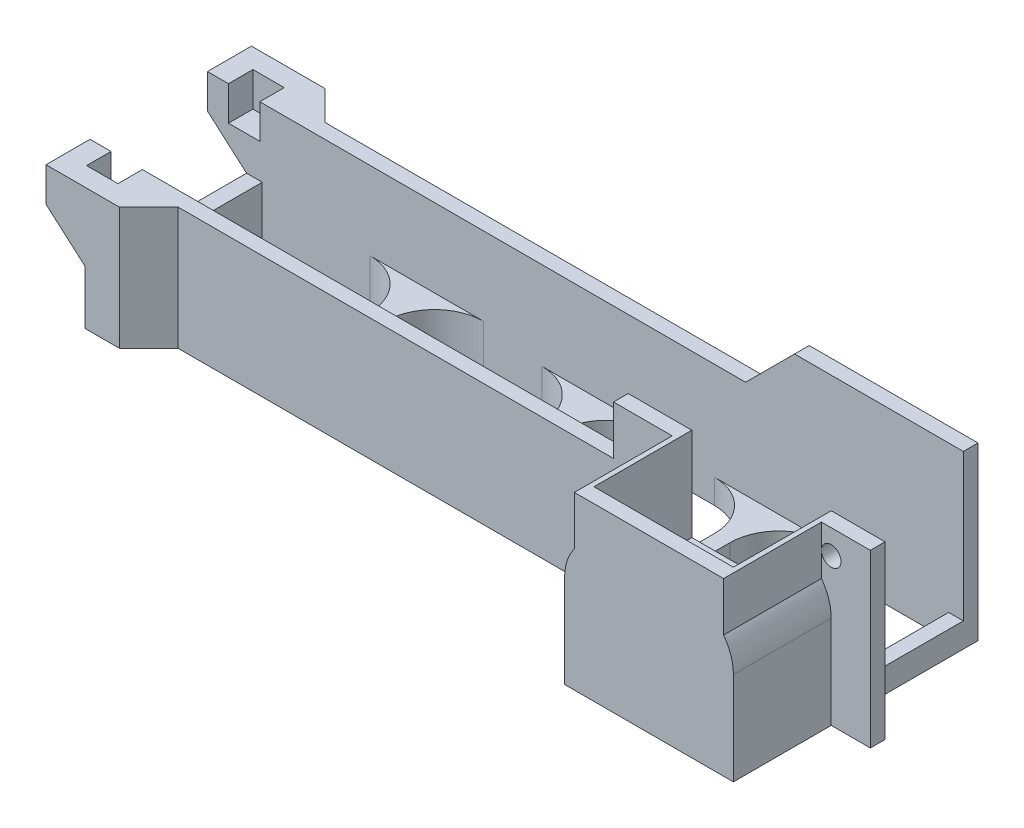
SolidWorks part; units mm, degrees
ref_plane "前视基准面" through (0, 0, 0) normal (0, 0, 1) x (1, 0, 0)
ref_plane "上视基准面" through (0, 0, 0) normal (0, 1, 0) x (1, 0, 0)
ref_plane "右视基准面" through (0, 0, 0) normal (1, 0, 0) x (0, 0, -1)
sketch "Sketch1" plane through (0, 0, 0) normal (0, 1, 0) x (1, 0, 0)
  line L1 (0, 0) -> (154.5, 0)
  line L2 (0, 0) -> (0, 30)
  line L3 (0, 30) -> (154.5, 30)
  line L4 (154.5, 0) -> (154.5, 30)
  line L5 (154.5, 0) -> (120, 0)
  line L6 (154.5, 0) -> (154.5, -20)
  line L7 (154.5, -20) -> (120, -20)
  line L8 (120, 0) -> (120, -20)
  dimension "D1" = 34.5
  dimension "D2" = 30
  dimension "D3" = 154.5
  dimension "D4" = 20
extrude "Boss-Extrude2" add sketch "Sketch1" along normal blind 1 contours L1 L4 L3 L2 | L1 L8 L7 L6 region at (77.25, 0, -15) region at (137.25, 0, 10)
sketch "Sketch2" plane through (0, 1, 0) normal (0, 1, 0) x (1, 0, 0)
  line L0 (3, 27) -> (0, 27)
  line L1 (0, 0) -> (120, 0)
  line L2 (120, 0) -> (120, -20) construction
  line L3 (0, 0) -> (120, 0) construction
  line L4 (120, 0) -> (120, -20)
  line L5 (120, -20) -> (154.5, -20)
  line L6 (0, 27) -> (0, 30)
  line L7 (154.5, 30) -> (0, 30)
  line L8 (151.5, 27) -> (154.5, 27)
  line L9 (3, 3) -> (123, 3)
  line L10 (123, 3) -> (123, -17)
  line L11 (123, -17) -> (151.5, -17)
  line L12 (154.5, -20) -> (154.5, 30) construction
  line L13 (151.5, 27) -> (3, 27)
  line L14 (3, 27) -> (3, 3) construction
  line L15 (0, 30) -> (0, 0) construction
  line L16 (151.5, -17) -> (151.5, 27) construction
  line L17 (154.5, -20) -> (154.5, 30) construction
  line L18 (154.5, 27) -> (154.5, 30)
  line L19 (151.5, -17) -> (151.5, 3)
  line L20 (151.5, 3) -> (154.5, 3)
  line L21 (154.5, 3) -> (154.5, -20)
  line L22 (3, 3) -> (0, 3)
  line L23 (0, 0) -> (0, 30) construction
  line L24 (0, 3) -> (0, 0)
  dimension "D1" = 3
extrude "Boss-Extrude5" add sketch "Sketch2" along normal blind 24
sketch "Sketch5" plane through (0, 0, -27) normal (0, 0, 1) x (1, 0, 0)
  line L0 (0, 0) -> (120, 0) construction
  line L1 (8, 1) -> (11.2, 1)
  line L2 (8, 1) -> (8, 11)
  line L3 (8, 11) -> (11.2, 11)
  line L4 (11.2, 1) -> (11.2, 11)
  line L8 (43.2, 1) -> (46.4, 1)
  line L9 (43.2, 1) -> (43.2, 9)
  line L10 (43.2, 9) -> (46.4, 9)
  line L11 (46.4, 1) -> (46.4, 9)
  line L12 (78.4, 1) -> (81.6, 1)
  line L13 (78.4, 1) -> (78.4, 7)
  line L14 (78.4, 7) -> (81.6, 7)
  line L15 (81.6, 1) -> (81.6, 7)
  line L16 (113.6, 1) -> (116.8, 1)
  line L17 (113.6, 1) -> (113.6, 5)
  line L18 (113.6, 5) -> (116.8, 5)
  line L19 (116.8, 1) -> (116.8, 5)
  line L20 (0, 25) -> (0, 0) construction
  line L21 (154.5, 1) -> (151.5, 1)
  line L22 (154.5, 1) -> (154.5, 5)
  line L23 (154.5, 5) -> (151.5, 5)
  line L26 (151.5, 1) -> (151.5, 5)
  dimension "D1" = 8
  dimension "D2" = 10
  dimension "D3" = 3.2
  dimension "D4" = 8
  dimension "D5" = 6
  dimension "D6" = 4
  dimension "D7" = 1
  dimension "D8" = 32
  dimension "D9" = 32
  dimension "D10" = 32
extrude "Boss-Extrude6" add sketch "Sketch5" along normal blind 24
sketch "Sketch6" plane through (0, 1, 0) normal (0, 1, 0) x (1, 0, 0)
  line L1 (123, 3) -> (151.5, 3)
  line L2 (123, 3) -> (123, -17)
  line L3 (123, -17) -> (151.5, -17)
  line L4 (151.5, 3) -> (151.5, -17)
extrude "Boss-Extrude7" add sketch "Sketch6" along normal blind 15
sketch "Sketch7" plane through (0, 25, 0) normal (0, 1, 0) x (1, 0, 0)
  line L0 (110, 3) -> (110, 0)
  line L1 (110, 0) -> (122, 0)
  line L2 (122, 0) -> (122, -20)
  line L3 (122, -20) -> (152.5, -20)
  line L4 (152.5, -20) -> (152.5, 0)
  line L6 (152.5, 0) -> (162.5, 0)
  line L7 (162.5, 0) -> (162.5, 3)
  line L8 (162.5, 3) -> (151.5, 3)
  line L9 (151.5, 3) -> (151.5, -17)
  line L10 (151.5, -17) -> (123, -17)
  line L11 (123, -17) -> (123, 3)
  line L12 (123, 3) -> (110, 3)
  dimension "D1" = 1
extrude "Boss-Extrude8" add sketch "Sketch7" along normal blind 10
sketch "Sketch9" plane through (0, 25, 0) normal (0, -1, 0) x (1, 0, 0)
  line L1 (154.5, -3) -> (162.5, -3)
  line L2 (154.5, -3) -> (154.5, 0)
  line L3 (154.5, 0) -> (162.5, 0)
  line L4 (162.5, -3) -> (162.5, 0)
extrude "Boss-Extrude9" add sketch "Sketch9" along normal blind 25
sketch "Sketch10" plane through (0, 0, -3) normal (0, 0, -1) x (-1, 0, 0)
  line L0 (-123, 16) -> (-123, 30) construction
  line L1 (-123, 35) -> (-123, 16) construction
  line L2 (-123, 30) -> (-120, 30) construction
  line L3 (-151.5, 16) -> (-151.5, 30) construction
  line L4 (-151.5, 35) -> (-151.5, 16) construction
  line L5 (-151.5, 30) -> (-154.5, 30) construction
  circle A0 centre (-120, 30) radius 2
  circle A1 centre (-154.5, 30) radius 2
extrude "Cut-Extrude1" cut sketch "Sketch10" against normal blind 8
sketch "Sketch11" plane through (0, 1, 0) normal (0, 1, 0) x (1, 0, 0)
  line L0 (11.2, 27) -> (43.2, 27)
  line L1 (43.2, 3) -> (11.2, 3)
  line L2 (11.2, 27) -> (11.2, 3)
  line L8 (43.2, 27) -> (43.2, 3)
  line L9 (46.4, 27) -> (78.4, 27)
  line L10 (46.4, 27) -> (46.4, 3)
  line L11 (46.4, 3) -> (78.4, 3)
  line L12 (78.4, 27) -> (78.4, 3)
  line L13 (81.6, 27) -> (113.6, 27)
  line L14 (81.6, 27) -> (81.6, 3)
  line L15 (81.6, 3) -> (113.6, 3)
  line L16 (113.6, 27) -> (113.6, 3)
  line L17 (116.8, 27) -> (151.5, 27)
  line L18 (116.8, 27) -> (116.8, 3)
  line L19 (116.8, 3) -> (151.5, 3)
  line L20 (151.5, 27) -> (151.5, 3)
extrude "Cut-Extrude2" cut sketch "Sketch11" against normal blind 8
fillet "Fillet1" radius 10 14 edges at (154.5, 25, 10) (120, 25, 10) (46.4, 4.5, -3) (81.6, 3.5, -3) (116.8, 2.5, -3) (113.6, 2.5, -27) (78.4, 3.5, -27) (43.2, 4.5, -27) (43.2, 4.5, -3) (113.6, 2.5, -3) (78.4, 3.5, -3) (46.4, 4.5, -27) (81.6, 3.5, -27) (116.8, 2.5, -27)
sketch "Sketch13" plane through (0, 0, 0) normal (0, -1, 0) x (1, 0, 0)
  line L2 (0, 0) -> (15, 0)
  line L3 (0, 0) -> (0, 6)
  line L4 (0, 6) -> (15, 6)
  line L5 (15, 0) -> (15, 6)
  dimension "D1" = 15
  dimension "D2" = 6
extrude "Boss-Extrude10" add sketch "Sketch13" against normal up to surface (25 mm away) up to face at (55, 25, -1.5)
sketch "Sketch15" plane through (0, 25, 0) normal (0, 1, 0) x (1, 0, 0)
  line L0 (110, 3) -> (0, 3) construction
  line L1 (4.3, 3) -> (10.7, 3)
  line L2 (4.3, 3) -> (4.3, -2)
  line L3 (4.3, -2) -> (10.7, -2)
  line L4 (10.7, 3) -> (10.7, -2)
  line L6 (15, -6) -> (0, -6) construction
  line L7 (7.5, -6) -> (7.5, 3) construction
  dimension "D1" = 6.4
  dimension "D2" = 5
extrude "Cut-Extrude3" cut sketch "Sketch15" against normal blind 7
ref_plane "Plane1" through (0, 0, -15) normal (0, 0, 1) x (1, 0, 0)
mirror "Mirror1" about plane through (0, 0, -15) normal (0, 0, 1) of "Cut-Extrude3", "Boss-Extrude10"
sketch "Sketch16" plane through (0, 0, -3) normal (0, 0, -1) x (-1, 0, 0)
  line L0 (-8, 11) -> (0, 18)
  line L1 (0, 25) -> (0, 1) construction
  line L2 (0, 18) -> (0, 0)
  line L3 (-8, 11) -> (-8, 0)
  line L4 (-15, 0) -> (-154.5, 0) construction
  line L5 (-8, 0) -> (0, 0)
  dimension "D1" = 18
extrude "Cut-Extrude4" cut sketch "Sketch16" against normal through all and the other way through all
chamfer "Chamfer1" distance 6 2 edges at (15, 12.5, 0)
sketch "Sketch17" plane through (0, 25, 0) normal (0, 1, 0) x (1, 0, 0)
  line L0 (10.7, 27) -> (154.5, 27) construction
  line L1 (154.5, 30) -> (120, 30)
  line L2 (154.5, 30) -> (154.5, 27)
  line L3 (154.5, 27) -> (120, 27)
  line L4 (120, 30) -> (120, 27)
  dimension "D1" = 34.5
extrude "Boss-Extrude11" add sketch "Sketch17" along normal up to surface (10 mm away) up to face at (136.9167, 35, 5.1667)
chamfer "Chamfer2" distance 10 angle 45 1 edges
